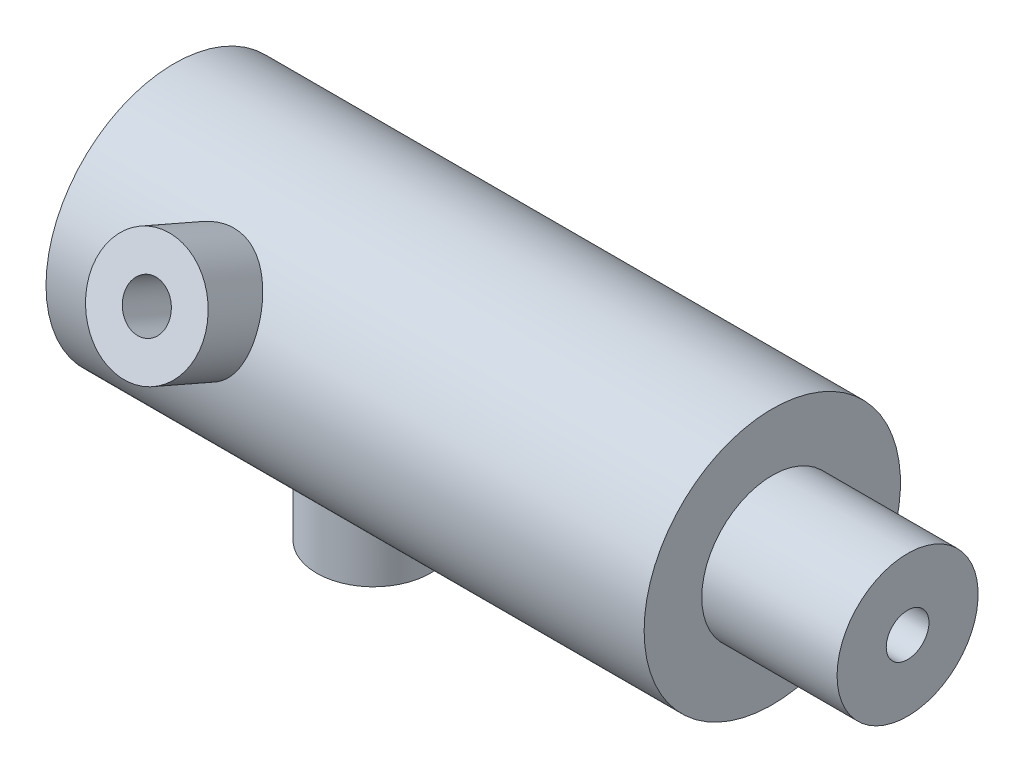
SolidWorks part; units mm, degrees
ref_plane "Front Plane" through (0, 0, 0) normal (0, 0, 1) x (1, 0, 0)
ref_plane "Top Plane" through (0, 0, 0) normal (0, 1, 0) x (1, 0, 0)
ref_plane "Right Plane" through (0, 0, 0) normal (1, 0, 0) x (0, 0, -1)
sketch "Body Sketch" plane through (0, 0, 0) normal (0, 0, 1) x (1, 0, 0)
  line L0 (-300, 0) -> (300, 0) construction
  line L1 (9.5, 0) -> (9.5, 4.953)
  line L2 (9.5, 4.953) -> (0, 4.953)
  line L3 (0, 4.953) -> (0, 9)
  line L4 (0, 9) -> (-42, 9)
  line L5 (-42, 9) -> (-42, 0)
  line L6 (-42, 0) -> (9.5, 0)
revolve "Body" add sketch "Body Sketch" angle 360 about L0
ref_axis "Engine Axis" through (12.075, 0, 0) along (-1, 0, 0)
sketch "Nitrous Boss Sketch" plane through (0, 0, 0) normal (0, 0, 1) x (1, 0, 0)
  line L0 (-28, -3) -> (-28, -16) construction
  line L1 (-28, -6) -> (-24, -6)
  line L2 (-24, -6) -> (-24, -13)
  line L3 (-24, -13) -> (-28, -13)
  line L4 (-28, -13) -> (-28, -6)
revolve "Nitrous Boss" add sketch "Nitrous Boss Sketch" angle 360 about L0
ref_plane "Ethanol Boss Plane" through (0, 0, 0) normal (0, -0.9169, 0.3991) x (-1, 0, 0)
sketch "Ethanol Boss Sketch" plane through (0, 0, 0) normal (0, -0.9169, 0.3991) x (-1, 0, 0)
  line L0 (32, -3) -> (32, -16) construction
  line L1 (32, -6) -> (28, -6)
  line L2 (28, -6) -> (28, -13)
  line L3 (28, -13) -> (32, -13)
  line L4 (32, -13) -> (32, -6)
revolve "Ethanol Boss" add sketch "Ethanol Boss Sketch" angle 360 about L0
sketch "Chamber Sketch" plane through (0, 0, 0) normal (0, 0, 1) x (1, 0, 0)
  line L0 (-300, 0) -> (300, 0) construction
  line L1 (-33.4, 0) -> (-6, 0)
  line L2 (-6, 0) -> (-6, 5)
  line L3 (-6, 5) -> (-33.4, 5)
  line L4 (-33.4, 5) -> (-33.4, 0)
revolve "Chamber" cut sketch "Chamber Sketch" angle 360 about L0
sketch "Flame Passage Sketch" plane through (0, 0, 0) normal (0, 0, 1) x (1, 0, 0)
  line L0 (-300, 0) -> (300, 0) construction
  line L1 (-6, 0) -> (10.5, 0)
  line L2 (10.5, 0) -> (10.5, 1.5)
  line L3 (10.5, 1.5) -> (-6, 1.5)
  line L4 (-6, 1.5) -> (-6, 0)
revolve "Flame Passage" cut sketch "Flame Passage Sketch" angle 360 about L0
sketch "Plug Hole Sketch" plane through (0, 0, 0) normal (0, 0, 1) x (1, 0, 0)
  line L0 (-300, 0) -> (300, 0) construction
  line L1 (-43, 0) -> (-33.4, 0)
  line L2 (-33.4, 0) -> (-33.4, 4.5)
  line L3 (-33.4, 4.5) -> (-43, 4.5)
  line L4 (-43, 4.5) -> (-43, 0)
revolve "Plug Hole" cut sketch "Plug Hole Sketch" angle 360 about L0
sketch "Nitrous Socket Sketch" plane through (0, 0, 0) normal (0, 0, 1) x (1, 0, 0)
  line L0 (-28, -4) -> (-28, -17) construction
  line L1 (-28, -7) -> (-26.4, -7)
  line L2 (-26.4, -7) -> (-26.4, -14)
  line L3 (-26.4, -14) -> (-28, -14)
  line L4 (-28, -14) -> (-28, -7)
revolve "Nitrous Socket" cut sketch "Nitrous Socket Sketch" angle 360 about L0
sketch "Nitrous Orifice Sketch" plane through (0, 0, 0) normal (0, 0, 1) x (1, 0, 0)
  line L0 (-28, -1.5) -> (-28, -10) construction
  line L1 (-28, -4.5) -> (-27.5, -4.5)
  line L2 (-27.5, -4.5) -> (-27.5, -7)
  line L3 (-27.5, -7) -> (-28, -7)
  line L4 (-28, -7) -> (-28, -4.5)
revolve "Nitrous Orifice" cut sketch "Nitrous Orifice Sketch" angle 360 about L0
ref_plane "Ethanol Socket Plane" through (0, 0, 0) normal (0, -0.9169, 0.3991) x (-1, 0, 0)
sketch "Ethanol Socket Sketch" plane through (0, 0, 0) normal (0, -0.9169, 0.3991) x (-1, 0, 0)
  line L0 (32, -4) -> (32, -17) construction
  line L1 (32, -7) -> (30.4, -7)
  line L2 (30.4, -7) -> (30.4, -14)
  line L3 (30.4, -14) -> (32, -14)
  line L4 (32, -14) -> (32, -7)
revolve "Ethanol Socket" cut sketch "Ethanol Socket Sketch" angle 360 about L0
ref_plane "Ethanol Orifice Plane" through (0, 0, 0) normal (0, -0.9169, 0.3991) x (-1, 0, 0)
sketch "Ethanol Orifice Sketch" plane through (0, 0, 0) normal (0, -0.9169, 0.3991) x (-1, 0, 0)
  line L0 (32, -1.5) -> (32, -10) construction
  line L1 (32, -4.5) -> (31.5, -4.5)
  line L2 (31.5, -4.5) -> (31.5, -7)
  line L3 (31.5, -7) -> (32, -7)
  line L4 (32, -7) -> (32, -4.5)
revolve "Ethanol Orifice" cut sketch "Ethanol Orifice Sketch" angle 360 about L0
sketch "Nitrous Socket Relief Sketch" plane through (0, 0, 0) normal (0, 0, 1) x (1, 0, 0)
  line L0 (-28, -18) -> (-28, -8) construction
  line L1 (-28, -14) -> (-26.2, -14)
  line L2 (-26.2, -14) -> (-26.2, -12.5)
  line L3 (-26.2, -12.5) -> (-28, -12.5)
  line L4 (-28, -12.5) -> (-28, -14)
revolve "Nitrous Socket Relief" cut sketch "Nitrous Socket Relief Sketch" angle 360 about L0
